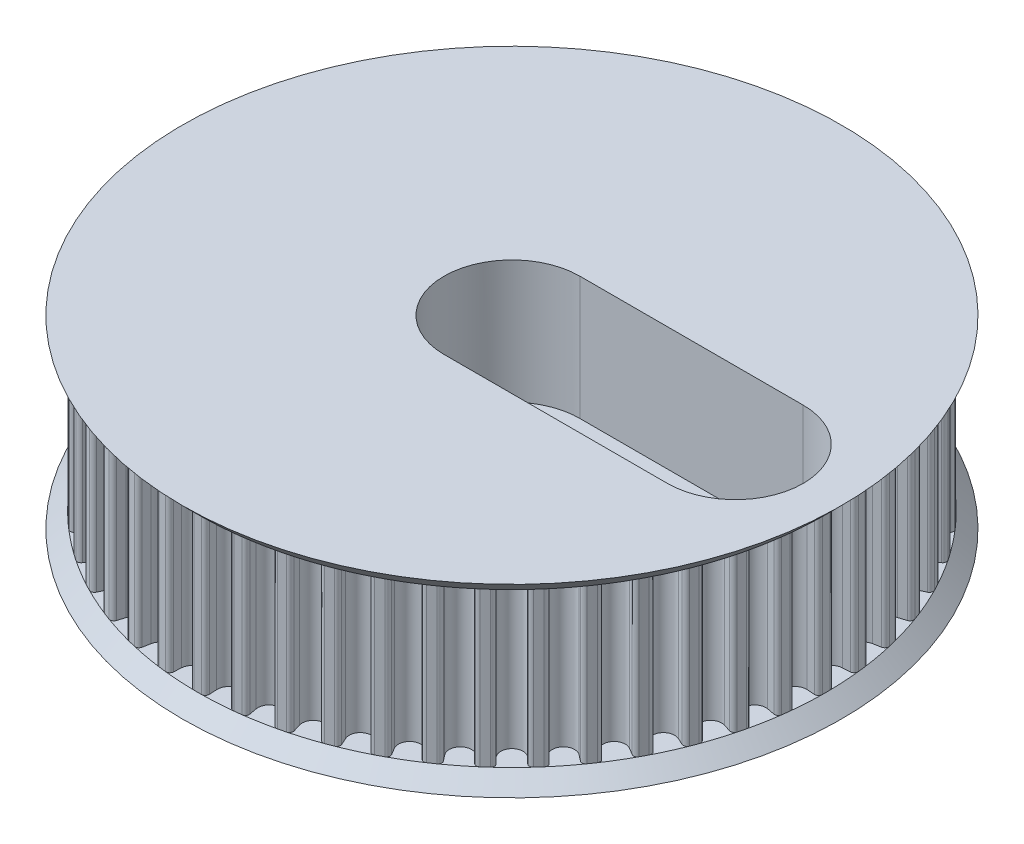
SolidWorks part; units mm, degrees
ref_plane "Front Plane" through (0, 0, 0) normal (0, 0, 1) x (1, 0, 0)
ref_plane "Top Plane" through (0, 0, 0) normal (0, 1, 0) x (1, 0, 0)
ref_plane "Right Plane" through (0, 0, 0) normal (1, 0, 0) x (0, 0, -1)
sketch "Sketch5" plane through (0, 0, 0) normal (0, 1, 0) x (1, 0, 0)
  line L0 (0, 0) -> (0, 41.3803) construction
  line L1 (0, 0) -> (-4.9878, 41.0786) construction
  line L2 (-3.908, 40.5926) -> (-3.816, 39.0712)
  line L3 (-1.0133, 40.7677) -> (-0.9213, 39.2463)
  line L4 (-4.9155, 40.483) -> (0, 40.7803) construction
  line L5 (-2.4578, 40.6316) -> (-2.3687, 39.1587) construction
  circle A0 centre (0, 0) radius 41.3803 construction
  circle A4 centre (0, 0) radius 40.7803
  circle A6 centre (0, 0) radius 37.7803 construction
  arc A7 (-3.816, 39.0712) -> (-0.9213, 39.2463) centre (-2.3687, 39.1587) ccw
  dimension "D1" = 82.7606
  dimension "D2" = 1.45
  dimension "D5" = 0.6
  dimension "D6" = 6.923
  dimension "D8" = 3
ref_axis "Axis1" through (0, 36.9714, 0) along (0, -1, 0)
extrude "Boss-Extrude1" add sketch "Sketch5" along normal mid plane 20 contours A7 L2 A4 L3 | L2 A7 L3 A4 region at (-2.3796, 0, -39.3401) region at (0.0035, 0, 0.0586)
extrude "Cut-Extrude1" cut sketch "Sketch5<3>" against normal through all and the other way through all contours L2 A7 L3 A4 region at (-2.3796, 0, -39.3401)
sketch "Sketch5<3>" plane through (0, 0, 0) normal (0, 1, 0) x (1, 0, 0) same geometry as "Sketch5"
fillet "Fillet1" radius 0.5 2 edges at (-3.908, 0, -40.5926) (-1.0133, 0, -40.7677)
pattern_circular "CirPattern1" count 52 over 360 about axis through (0, 36.9714, 0) along (0, -1, 0) of "Fillet1", "Cut-Extrude1"
sketch "Sketch7" plane through (0, 0, 0) normal (0, 0, 1) x (1, 0, 0)
  line L0 (0, 12) -> (0, 10)
  line L1 (0, 10) -> (40.7803, 10)
  line L2 (40.7803, 10) -> (42.7803, 12)
  line L3 (42.7803, 12) -> (0, 12)
  point P3 (45.3803, 26.0572)
  dimension "D1" = 40.7803
  dimension "D2" = 2
  dimension "D3" = 45
  dimension "D4" = 10
revolve "Revolve1" add sketch "Sketch7" angle 360 about axis through (0, 36.9714, 0) along (0, -1, 0)
mirror "Mirror1" about plane through (0, 0, 0) normal (0, 1, 0) of "Revolve1"
sketch "Sketch8" plane through (0, 0, 0) normal (0, 1, 0) x (1, 0, 0)
  line L0 (0, 0) -> (15.4741, 0) construction
  line L1 (0, 0) -> (5.1265, 5.1265) construction
  circle A0 centre (0, 0) radius 5
  circle A1 centre (5.1265, 5.1265) radius 1.55
  circle A2 centre (5.1265, -5.1265) radius 1.55
  circle A3 centre (-5.1265, -5.1265) radius 1.55
  circle A4 centre (-5.1265, 5.1265) radius 1.55
  point P5 (-17.9809, 11.6375)
  point P6 (0, 0)
  point P15 (0, 0)
  dimension "D1" = 3.1
  dimension "D3" = 10
  dimension "D2" = 7.25
  dimension "D4" = 4
  dimension "D5" = 45
extrude "Cut-Extrude2" cut sketch "Sketch8" against normal through all and the other way through all
sketch "Sketch9" plane through (0, 12, 0) normal (0, 1, 0) x (1, 0, 0)
  line L0 (0, 0) -> (29, 0) construction
  line L1 (0, 8.8084) -> (29, 8.8084)
  line L2 (0, -8.8084) -> (29, -8.8084)
  arc A1 (0, 8.8084) -> (0, -8.8084) centre (0, 0) ccw
  arc A2 (29, -8.8084) -> (29, 8.8084) centre (29, 0) ccw
  point P3 (14.5, 0)
  dimension "D1" = 29
extrude "Cut-Extrude3" cut sketch "Sketch9" against normal blind 16
equation "\"Pitch\"= 5mm"
equation "\"ToothNum\"= 52"
equation "\"Angle\"= 360deg / \"ToothNum\""
equation "\"PitchDiam\"= ( \"Pitch\" * \"ToothNum\" ) / pi"
equation "\"D1@Sketch5\"=\"PitchDiam\""
equation "\"D6@Sketch5\"=\"Angle\""
equation "\"GearHeight\"= 20"
equation "\"D1@Boss-Extrude1\"=\"GearHeight\""
equation "\"D1@Fillet1\"=\"Pitch\"/10"
equation "\"D1@CirPattern1\"=\"ToothNum\""
equation "\"D1@Sketch7\"=\"PitchDiam\"/2 - \"Margin\""
equation "\"D4@Sketch7\"=\"GearHeight\"/2"
equation "\"Margin\"=0.6"
equation "\"D5@Sketch5\"=\"Margin\""
